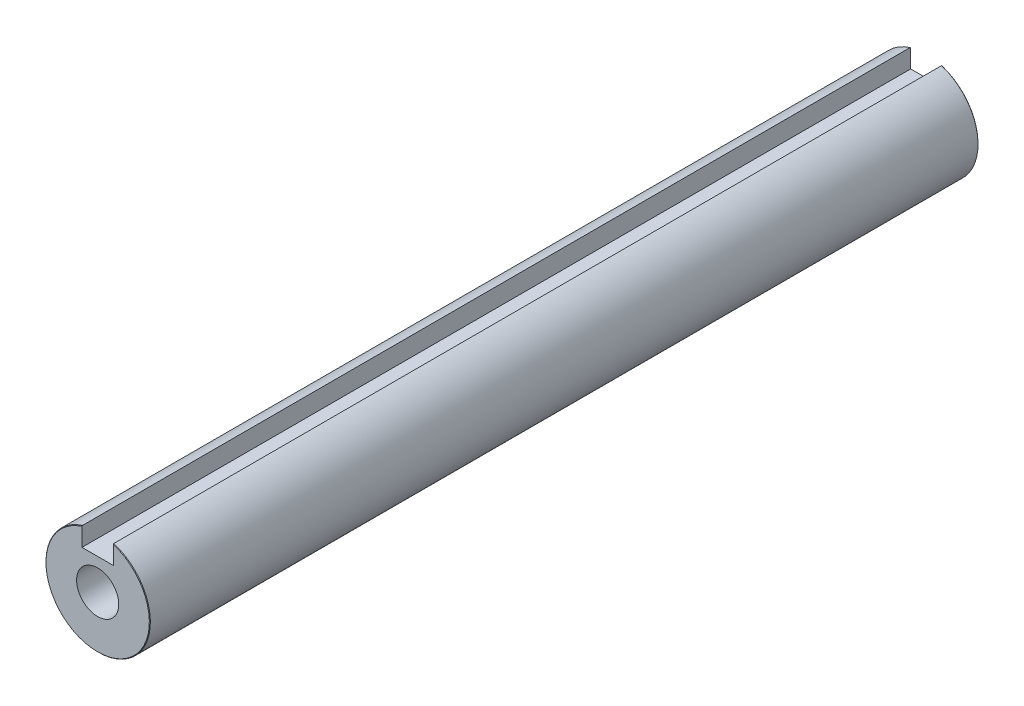
SolidWorks part; units mm, degrees
ref_plane "Front Plane" through (0, 0, 0) normal (0, 0, 1) x (1, 0, 0)
ref_plane "Top Plane" through (0, 0, 0) normal (0, 1, 0) x (1, 0, 0)
ref_plane "Right Plane" through (0, 0, 0) normal (1, 0, 0) x (0, 0, -1)
sketch "Sketch1" plane through (0, 0, 0) normal (1, 0, 0) x (0, 0, -1)
  line L0 (0, 0) -> (0, 5) construction
  line L1 (-39.6875, 5) -> (39.6875, 5)
  line L2 (-39.6875, 5) -> (-39.6875, -5)
  line L3 (-39.6875, -5) -> (39.6875, -5)
  line L4 (39.6875, 5) -> (39.6875, -5)
  line L5 (-39.6875, 5) -> (39.6875, -5) construction
  line L6 (-39.6875, -5) -> (39.6875, 5) construction
  line L7 (0, 0) -> (0, -5) construction
  point P0 (0, 0)
  point P8 (-28.1875, 5)
  point P10 (28.1875, 5)
  point P11 (-24.3542, -5)
  point P12 (26.4085, -5)
  dimension "Diameter" = 10
  dimension "Length" = 79.375
  dimension "D1" = 11.5
  dimension "D2" = 11.5
  dimension "Keyway Length" = 79.375
  dimension "D3" = 13.279
  dimension "D5" = 15.3333
sketch "Sketch2" plane through (0, 0, 0) normal (0, 0, 1) x (1, 0, 0)
  line L0 (0, 0) -> (0, 5) construction
  line L2 (1.5, 2.9697) -> (-1.5, 2.9697)
  line L3 (1.5, 2.9697) -> (1.5, 4.7697)
  line L4 (1.5, 4.7697) -> (-1.5, 4.7697)
  line L5 (-1.5, 2.9697) -> (-1.5, 4.7697)
  line L6 (1.5, 2.9697) -> (-1.5, 4.7697) construction
  line L7 (1.5, 4.7697) -> (-1.5, 2.9697) construction
  circle A0 centre (0, 0) radius 5
  point P3 (0, 3.8697)
  dimension "Keyway Width" = 3
  dimension "Keyway Depth" = 1.8
sketch "Sketch3" plane through (0, 0, 0) normal (0, 0, 1) x (1, 0, 0)
  line L1 (-1.5, 2.9697) -> (-1.5, 4.7697) construction
  line L2 (1.5, 2.9697) -> (-1.5, 2.9697) construction
  line L3 (1.5, 2.9697) -> (1.5, 4.7697) construction
  line L5 (-1.5, 2.9697) -> (-1.5, 4.7697)
  line L6 (1.5, 2.9697) -> (-1.5, 2.9697)
  line L7 (1.5, 2.9697) -> (1.5, 4.7697)
  circle A0 centre (0, 0) radius 5 construction
  arc A1 (-1.5, 4.7697) -> (1.5, 4.7697) centre (0, 0) ccw
extrude "Boss-Extrude1" add sketch "Sketch3" along normal up to vertex (39.6875 mm away) and the other way up to vertex (39.6875 mm away) up to point (0, 5, 39.6875) other way up to point (0, 5, -39.6875)
chamfer "Chamfer1" distance 0.05 angle 45 2 edges at (0, -5, 39.6875) (0, -5, -39.6875)
hole_wizard "Tap Drill for #10-32 Tap1" positions "3DSketch1" profile "Sketch4" hole size "#10-32" standard "ANSI Inch"
sketch3d "3DSketch1"
  arc A0 (1.5, 4.7173, -39.6875) -> (-1.5, 4.7173, -39.6875) centre (0, 0, -39.6875) ccw construction
  arc A1 (-1.5, 4.7173, 39.6875) -> (1.5, 4.7173, 39.6875) centre (0, 0, 39.6875) ccw construction
  point P0 (0, 0, 39.6875)
  point P2 (0, 0, -39.6875)
  point P8 (0, 0, -44.6375)
  point P13 (0, 0, 44.6375)
sketch "Sketch4" plane through (0, 0, 39.6875) normal (1, 0, 0) x (0, -1, 0)
  line L0 (0, 0) -> (0, 12.3258)
  line L1 (0, 12.3258) -> (2.0193, 11.1125)
  line L2 (2.0193, 11.1125) -> (2.0193, 0)
  line L5 (2.0193, 0) -> (0, 0)
  line L10 (0, 12.3258) -> (-2.0193, 11.1125) construction
  line L11 (0, -6.35) -> (0, 107.95) construction
  dimension "Hole Dia." = 4.0386
  dimension "Hole Depth" = 11.1125
  dimension "Drill Angle" = 118
equation "\"D2@Sketch1\"=1.15*\"Diameter@Sketch1\""
equation "\"D1@Sketch1\"=\"D2@Sketch1\""
equation "\"D1@Chamfer1\"=\"Diameter@Sketch1\"*.005"
equation "\"D3@Sketch1\"=\"D2@Sketch1\"/(2*tan(.5236*180/pi))*4/3"
equation "\"D5@Sketch1\" = 4 / 3 * \"D2@Sketch1\""
